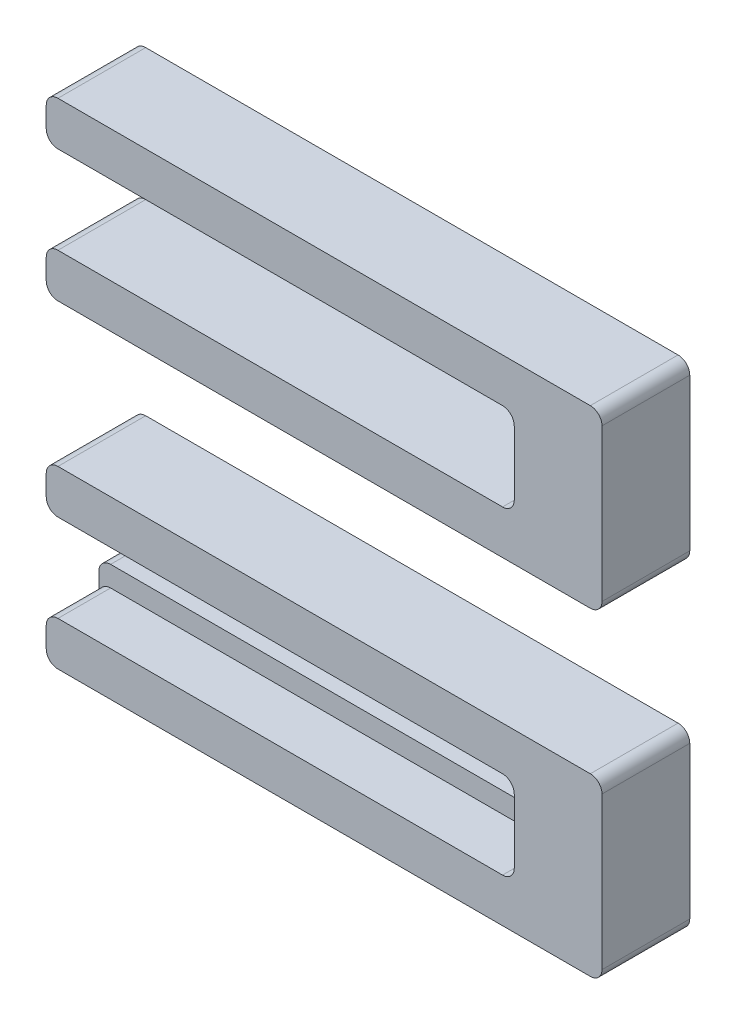
SolidWorks part; units mm, degrees
ref_plane "Front Plane" through (0, 0, 0) normal (0, 0, 1) x (1, 0, 0)
ref_plane "Top Plane" through (0, 0, 0) normal (0, 1, 0) x (1, 0, 0)
ref_plane "Right Plane" through (0, 0, 0) normal (1, 0, 0) x (0, 0, -1)
sketch "Sketch2" plane through (0, 0, 0) normal (0, 0, 1) x (1, 0, 0)
  line L0 (-2.7742, -2.4497) -> (31.3823, -2.4497) construction
  line L1 (0, 0) -> (19, 0)
  line L2 (0, 0) -> (0, 6)
  line L3 (0, 6) -> (19, 6)
  line L4 (19, 0) -> (19, 6)
  line L5 (0, 4.5) -> (16, 4.5)
  line L6 (0, 4.5) -> (0, 1.5)
  line L7 (0, 1.5) -> (16, 1.5)
  line L8 (16, 4.5) -> (16, 1.5)
  line L9 (0, 4.5) -> (16, 4.5)
  line L10 (0, 4.5) -> (0, 3.8)
  line L11 (0, 3.8) -> (16, 3.8)
  line L12 (16, 4.5) -> (16, 3.8)
  line L13 (16, -9.3995) -> (16, -8.6995)
  line L14 (0, -8.6995) -> (16, -8.6995)
  line L15 (0, -9.3995) -> (0, -8.6995)
  line L16 (0, -9.3995) -> (16, -9.3995)
  line L17 (16, -9.3995) -> (16, -6.3995)
  line L18 (0, -6.3995) -> (16, -6.3995)
  line L19 (0, -9.3995) -> (0, -6.3995)
  line L20 (0, -9.3995) -> (16, -9.3995)
  line L21 (19, -4.8995) -> (19, -10.8995)
  line L22 (0, -10.8995) -> (19, -10.8995)
  line L23 (0, -4.8995) -> (0, -10.8995)
  line L24 (0, -4.8995) -> (19, -4.8995)
  dimension "D1" = 6
  dimension "D2" = 3
  dimension "D3" = 1.5
  dimension "D4" = 3
  dimension "D5" = 16
  dimension "D6" = 2.3
extrude "Boss-Extrude1" add sketch "Sketch2" along normal blind 3 contours L5 L8 L7 L2 L1 L4 L3 | L24 L23 L18 L17 L13 L16 L22 L21 region at (0.1992, 0.75, 0) region at (16.1992, -9.0495, 0)
extrude "Boss-Extrude3" add sketch "Sketch2<4>" along normal blind 1.2 contours L15 L16 L13 L14 | L6 L11 L8 L5 region at (8, 4.15, 0) region at (8, -9.0495, 0)
sketch "Sketch2<4>" plane through (0, 0, 0) normal (0, 0, 1) x (1, 0, 0) same geometry as "Sketch2"
fillet "Fillet2" radius 0.4 10 edges at (0, 4.5, 2.1) (16, 1.5, 1.5) (16, 3.8, 0.6) (16, 4.5, 2.1) (19, 6, 1.5) (19, 0, 1.5) (0, 0, 1.5) (0, 1.5, 1.5) (0, 3.8, 0.6) (0, 6, 1.5)
fillet "Fillet3" radius 0.4 10 edges at (19, -10.8995, 1.5) (19, -4.8995, 1.5) (16, -6.3995, 1.5) (16, -9.3995, 2.1) (16, -8.6995, 0.6) (0, -10.8995, 1.5) (0, -9.3995, 2.1) (0, -8.6995, 0.6) (0, -4.8995, 1.5) (0, -6.3995, 1.5)
